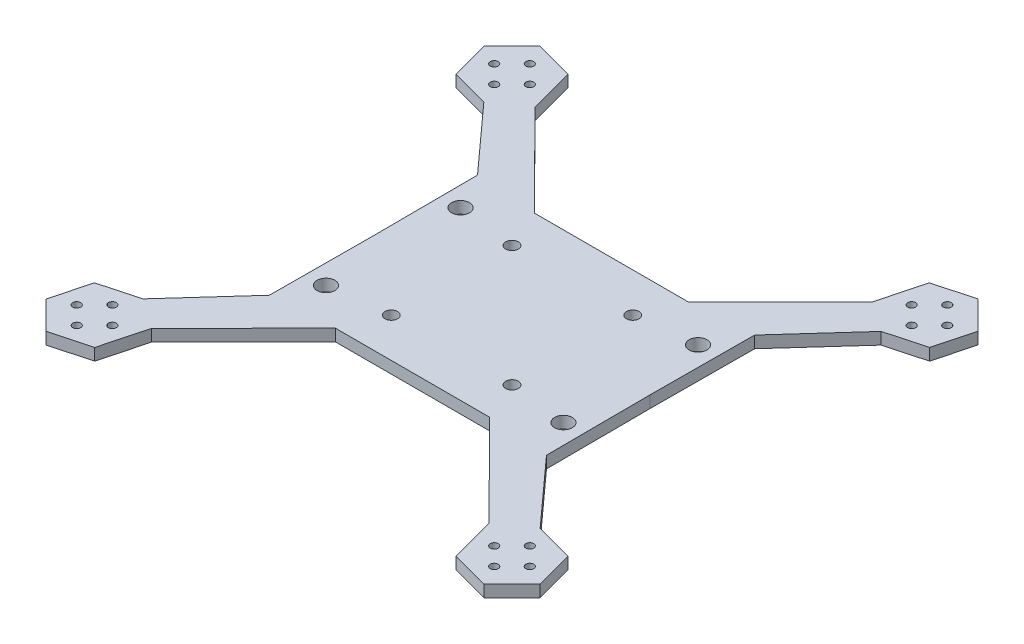
SolidWorks part; units mm, degrees
ref_plane "Front Plane" through (0, 0, 0) normal (0, 0, 1) x (1, 0, 0)
ref_plane "Top Plane" through (0, 0, 0) normal (0, 1, 0) x (1, 0, 0)
ref_plane "Right Plane" through (0, 0, 0) normal (1, 0, 0) x (0, 0, -1)
sketch "Sketch1" plane through (0, 0, 0) normal (0, 1, 0) x (1, 0, 0)
  line L5 (-35, -35) -> (42.6186, 42.6186) construction
  line L6 (-35, 35) -> (35, -35) construction
  line L9 (0, 0) -> (42.4264, 42.4264) construction
  line L10 (52.7307, 48.2307) -> (52.7307, 57.2307) construction
  line L11 (30, 17) -> (30, 0) construction
  line L12 (0, 0) -> (0, 23.6863) construction
  line L28 (0, 0) -> (-174.2372, 0) construction
  line L41 (31.9599, 25.1581) -> (-25.1581, 25.1581) construction
  line L70 (42.6186, 48.4021) -> (19.4638, 25.1581)
  line L72 (48.2307, 52.7307) -> (57.2307, 52.7307) construction
  line L74 (48.2307, 52.7307) -> (52.7307, 48.2307) construction
  line L75 (55.3003, 62.3949) -> (45.646, 59.7881)
  line L77 (45.646, 59.7881) -> (42.6186, 48.4021)
  line L80 (50.185, 43.0729) -> (59.8153, 45.6732)
  line L83 (59.8153, 45.6732) -> (62.3849, 55.3374)
  line L85 (62.3849, 55.3374) -> (55.3003, 62.3949)
  line L87 (50.185, 43.0729) -> (35, 26.2883)
  line L88 (35, 26.2883) -> (34.873, 0)
  line L89 (34.873, -11.873) -> (34.873, 11.873) construction
  line L90 (-21.8355, 25.1581) -> (21.8355, 25.1581)
  line L94 (35, -26.2883) -> (34.873, 0)
  line L100 (48.2307, -52.7307) -> (52.7307, -48.2307) construction
  line L101 (48.2307, -52.7307) -> (57.2307, -52.7307) construction
  line L102 (52.7307, -48.2307) -> (52.7307, -57.2307) construction
  line L106 (62.3849, -55.3374) -> (55.3003, -62.3949)
  line L111 (59.8153, -45.6732) -> (62.3849, -55.3374)
  line L115 (50.185, -43.0729) -> (59.8153, -45.6732)
  line L116 (45.646, -59.7881) -> (42.6186, -48.4021)
  line L119 (55.3003, -62.3949) -> (45.646, -59.7881)
  line L127 (50.185, -43.0729) -> (35, -26.2883)
  line L128 (35, 26.2883) -> (34.873, 0)
  line L129 (35, -26.2883) -> (34.873, 0)
  line L135 (42.6186, -48.4021) -> (19.4638, -25.1581)
  line L138 (40.4517, 52.7386) -> (49.1512, 44.0725) [skipped]
  line L139 (-21.8355, -25.1581) -> (21.8355, -25.1581)
  line L140 (-48.2307, 52.7307) -> (-52.7307, 48.2307) construction
  line L141 (-48.2307, 52.7307) -> (-57.2307, 52.7307) construction
  line L142 (-52.7307, 48.2307) -> (-52.7307, 57.2307) construction
  line L143 (-62.3849, 55.3374) -> (-55.3003, 62.3949)
  line L144 (-59.8153, 45.6732) -> (-62.3849, 55.3374)
  line L145 (-50.185, 43.0729) -> (-59.8153, 45.6732)
  line L146 (-45.646, 59.7881) -> (-42.6186, 48.4021)
  line L147 (-55.3003, 62.3949) -> (-45.646, 59.7881)
  line L148 (-50.185, 43.0729) -> (-35, 26.2883)
  line L149 (-42.6186, 48.4021) -> (-19.4638, 25.1581)
  line L150 (-35, 26.2883) -> (-34.873, 0)
  line L151 (-35, -26.2883) -> (-34.873, 0)
  line L152 (-50.185, -43.0729) -> (-35, -26.2883)
  line L153 (-42.6186, -48.4021) -> (-19.4638, -25.1581)
  line L154 (-52.7307, -48.2307) -> (-52.7307, -57.2307) construction
  line L155 (-48.2307, -52.7307) -> (-57.2307, -52.7307) construction
  line L156 (-48.2307, -52.7307) -> (-52.7307, -48.2307) construction
  line L157 (-55.3003, -62.3949) -> (-45.646, -59.7881)
  line L158 (-45.646, -59.7881) -> (-42.6186, -48.4021)
  line L159 (-50.185, -43.0729) -> (-59.8153, -45.6732)
  line L160 (-59.8153, -45.6732) -> (-62.3849, -55.3374)
  line L161 (-62.3849, -55.3374) -> (-55.3003, -62.3949)
  circle A0 centre (-15.25, 15.25) radius 1.6
  circle A1 centre (15.25, 15.25) radius 1.6
  circle A2 centre (15.25, -15.25) radius 1.6
  circle A3 centre (-15.25, -15.25) radius 1.6
  circle A18 centre (30, 17) radius 2.25
  circle A19 centre (30, -17) radius 2.25
  circle A20 centre (-30, -17) radius 2.25
  circle A21 centre (-30, 17) radius 2.25
  circle A69 centre (52.7307, 52.7307) radius 8.6603 construction
  circle A70 centre (52.7307, 57.2307) radius 1
  circle A71 centre (52.7307, 48.2307) radius 1
  circle A72 centre (48.2307, 52.7307) radius 1
  circle A73 centre (57.2307, 52.7307) radius 1
  circle A124 centre (52.7307, -52.7307) radius 8.6603 construction
  circle A125 centre (57.2307, -52.7307) radius 1
  circle A126 centre (48.2307, -52.7307) radius 1
  circle A127 centre (52.7307, -48.2307) radius 1
  circle A128 centre (52.7307, -57.2307) radius 1
  circle A129 centre (-52.7307, 52.7307) radius 8.6603 construction
  circle A130 centre (-57.2307, 52.7307) radius 1
  circle A131 centre (-48.2307, 52.7307) radius 1
  circle A132 centre (-52.7307, 48.2307) radius 1
  circle A133 centre (-52.7307, 57.2307) radius 1
  circle A134 centre (-52.7307, -52.7307) radius 8.6603 construction
  circle A135 centre (-52.7307, -57.2307) radius 1
  circle A136 centre (-52.7307, -48.2307) radius 1
  circle A137 centre (-48.2307, -52.7307) radius 1
  circle A138 centre (-57.2307, -52.7307) radius 1
  point P0 (0, 0)
  point P8 (52.7307, 52.7307)
  point P9 (52.7307, 52.7307)
  point P17 (0, 0)
  point P45 (24.8566, 0)
  point P47 (30, 0)
  point P90 (0, 25.1581)
  point P95 (0, -25.1581)
  point P96 (0, 25.1581)
  point P99 (0, 25.1581)
  point P110 (0, -25.1581)
  point P118 (0, 0)
  point P126 (0, -25.1581)
  dimension "D3" = 3.2
  dimension "D16" = 4.5
  dimension "D1" = 70
  dimension "D2" = 4.5
  dimension "D4" = 30.5
  dimension "D6" = 4.5
  dimension "D7" = 20
  dimension "D15" = 17
  dimension "D12" = 30
  dimension "D5" = 4
  dimension "D17" = 2
extrude "Boss-Extrude1" add sketch "Sketch1" along normal blind 3 contours L144 A21 A0 A1 A2 A3 region at (0, 0, 0)
sketch "Sketch4" plane through (0, 0, 0) normal (0, -1, 0) x (1, 0, 0)
  circle A0 centre (0, 0) radius 4.9
  circle A1 centre (0, 0) radius 6.495
  dimension "D1" = 9.8
extrude "Boss-Extrude3" add sketch "Sketch4" along normal blind 5
sketch "Sketch6" plane through (0, 0, 25.1581) normal (0, 0, 1) x (1, 0, 0)
  line L0 (-6.495, 0) -> (6.495, 0) construction
  line L1 (-4.2416, -1.8916) -> (4.2416, -1.8916)
  line L2 (-4.2416, -1.8916) -> (-4.2416, 0)
  line L3 (-4.2416, 0) -> (4.2416, 0)
  line L4 (4.2416, -1.8916) -> (4.2416, 0)
  line L5 (-4.2416, -1.8916) -> (4.2416, 0) construction
  line L6 (-4.2416, 0) -> (4.2416, -1.8916) construction
  point P0 (0, -0.9458)
extrude "Cut-Extrude3" cut sketch "Sketch6" against normal blind 34
